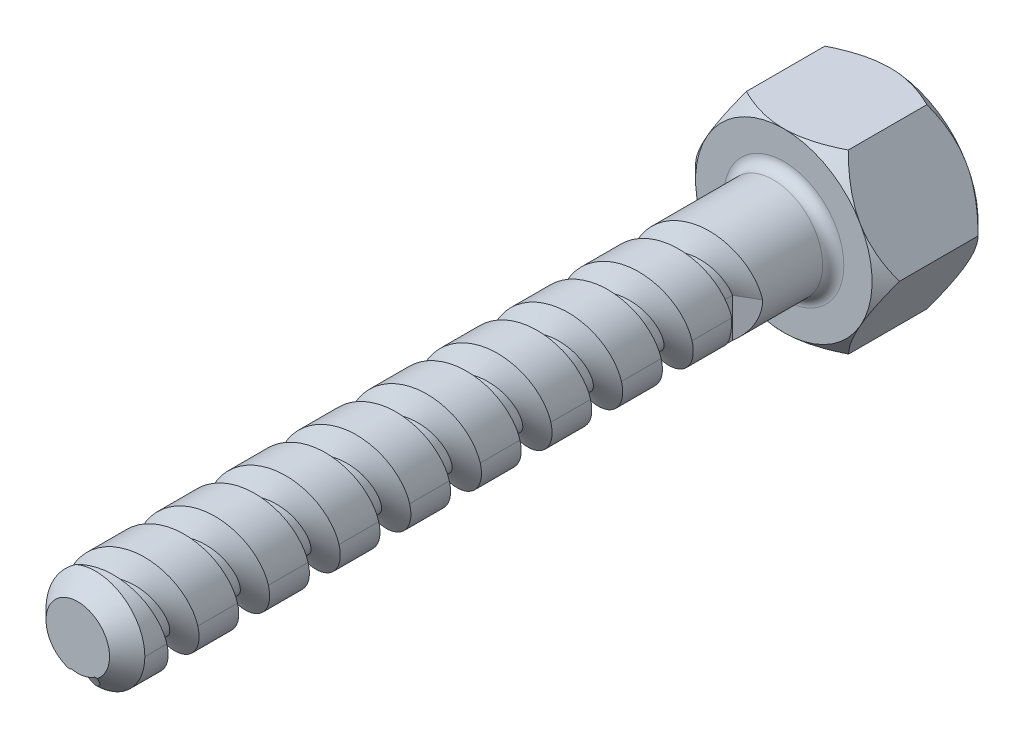
SolidWorks part; units mm, degrees
ref_plane "Front Plane" through (0, 0, 0) normal (0, 0, 1) x (1, 0, 0)
ref_plane "Top Plane" through (0, 0, 0) normal (0, 1, 0) x (1, 0, 0)
ref_plane "Right Plane" through (0, 0, 0) normal (1, 0, 0) x (0, 0, -1)
sketch "Sketch1" plane through (0, 0, 0) normal (0, 0, 1) x (1, 0, 0)
  line L1 (-1.4377, -2.5033) -> (1.449, -2.4967)
  line L2 (1.449, -2.4967) -> (2.8867, 0.0065)
  line L3 (2.8867, 0.0065) -> (1.4377, 2.5033)
  line L4 (1.4377, 2.5033) -> (-1.449, 2.4967)
  line L5 (-1.449, 2.4967) -> (-2.8867, -0.0065)
  line L6 (-2.8867, -0.0065) -> (-1.4377, -2.5033)
  circle A0 centre (0, 0) radius 2.5 construction
  dimension "D1" = 5
extrude "Boss-Extrude1" add sketch "Sketch1" along normal mid plane 3 contours L5 L6 L1 L2 L3 L4
sketch "Sketch2" plane through (0, 0, 1.5) normal (0, 0, 1) x (1, 0, 0)
  line L0 (-1.449, 2.4967) -> (-2.8867, -0.0065) construction
  circle A0 centre (0, 0) radius 2.5
extrude "Cut-Extrude1" cut sketch "Sketch2" against normal through all draft 45 flip side to cut
mirror "Mirror1" about plane through (0, 0, 0) normal (0, 0, 1) of "Cut-Extrude1"
sketch "Sketch3" plane through (0, 0, 1.5) normal (0, 0, 1) x (1, 0, 0)
  circle A0 centre (0, 0) radius 1.4
  dimension "D1" = 2.8
extrude "Boss-Extrude2" add sketch "Sketch3" along normal blind 20
chamfer "Chamfer1" distance 0.5 angle 45 1 edges at (1.4, 0, 21.5)
thread "Thread1" pitch 1 method cut profile "Thread Profile2" start angle 0, offset 2, length 0, pitch 2, diameter 2.8
ref_plane "Plane2" through (1.4, 0, 3.5) normal (0, -1, 0) x (1, 0, 0)
sketch "Thread Profile2" plane through (1.4, 0, 3.5) normal (0, -1, 0) x (1, 0, 0)
  line L0 (0, 0) -> (0, 1) construction
  line L11 (0, 0) -> (0, 0.875)
  line L12 (0, 0.875) -> (-0.5413, 0.5625)
  line L13 (-0.5413, 0.5625) -> (-0.5413, 0.3125)
  line L15 (-0.5413, 0.3125) -> (0, 0)
  line L17 (-0.5413, 0.4375) -> (0, 0.4375) construction
  point P2 (0, 0)
  dimension "Pitch" = 1
  dimension "Profile_Angle" = 60
  dimension "Profile_Land" = 0.25
  dimension "Profile_Height" = 0.5413
sketch "Sketch14" plane through (0, 0, 0) normal (0, 1, 0) x (1, 0, 0)
  line L4 (1.4, -3.5) -> (0.8587, -3.8125)
  line L5 (0.8587, -3.8125) -> (0.8587, -4.0625)
  line L6 (0.8587, -4.0625) -> (1.4, -4.375)
  line L7 (1.4, -4.375) -> (1.4, -3.5)
  line L8 (1.4, -3.5) -> (0.8587, -3.8125)
  line L9 (0.8587, -3.8125) -> (0.8587, -4.0625)
  line L10 (0.8587, -4.0625) -> (1.4, -4.375)
  line L11 (1.4, -4.375) -> (1.4, -3.5)
  dimension "D1" = 0
extrude "Cut-Extrude2" cut sketch "Sketch14" against normal through all
fillet "Fillet1" radius 0.3 1 edges at (1.4, 0, 1.5)
scale "Scale1" bodies to scale 106 scale about centroid uniform scaling yes scale factor 0.8
